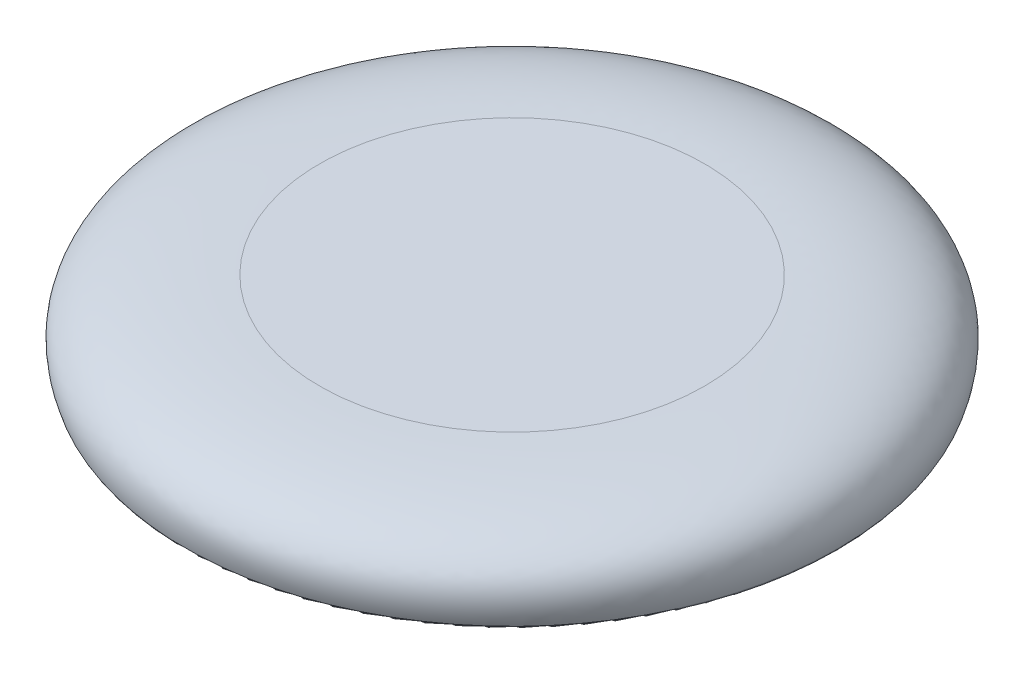
SolidWorks part; units mm, degrees
ref_plane "Front Plane" through (0, 0, 0) normal (0, 0, 1) x (1, 0, 0)
ref_plane "Top Plane" through (0, 0, 0) normal (0, 1, 0) x (1, 0, 0)
ref_plane "Right Plane" through (0, 0, 0) normal (1, 0, 0) x (0, 0, -1)
sketch "Sketch1" plane through (0, 0, 0) normal (0, 0, 1) x (1, 0, 0)
  line L1 (0, 32) -> (80, 32)
  line L3 (131, 0) -> (131.852, 16.2567)
  line L4 (131, 0) -> (135, 0)
  line L5 (0, 29) -> (80, 29)
  line L6 (0, 32) -> (0, 29)
  line L7 (0, 0) -> (0, 32) construction
  line L8 (137, 34.6801) -> (137, -28.1957) construction
  conic Q0 (80, 32) -> (135, 0) control (147.5, 32) rho 0.5
  spline S0 degree 1 poles (80, 29) (132.2056, 1.0916) knots 0 0 1 1 construction
  spline S1 degree 3 poles (80, 29) (80.6891, 29) (82.0769, 28.9948) (84.7752, 28.964) (88.0564, 28.8868) (91.83, 28.7327) (96.6483, 28.4456) (102.2677, 27.9344) (108.3611, 27.0808) (113.7984, 25.9923) (120.1638, 24.2404) (126.4441, 21.5153) (129.9403, 18.6716) (131.5643, 16.6883) (132.539, 15.2596) (133.4409, 13.2652) (133.9723, 10.6401) (133.9768, 8.2941) (133.7079, 6.243) (133.3643, 4.6176) (132.9545, 3.1882) (132.5531, 2.007) (132.3234, 1.3931) (132.2056, 1.0916) knots 0 0 0 0 0.015625 0.03125 0.0625 0.09375 0.125 0.1875 0.25 0.3125 0.375 0.5 0.625 0.647011 0.678261 0.75 0.8125 0.875 0.90625 0.9375 0.96875 0.984375 1 1 1 1 only from (80, 29) to (131.852, 16.2567)
  dimension "D5" = 67.5
  dimension "D1" = 80
  dimension "D2" = 135
  dimension "D3" = 32
  dimension "D6" = 4
  dimension "D8" = 87
  dimension "D9" = 137
  dimension "D7" = 3
revolve "Revolve1" add sketch "Sketch1" angle 360 about L7
fillet "Fillet1" radius 2 2 edges at (131, 0, 0) (135, 0, 0)
ref_plane "Edge Plane" through (0, 0, 138) normal (0, 0, 1) x (1, 0, 0)
ref_axis "Frisbee Pivot" through (160.6691, 0, 138) along (-1, 0, 0)
